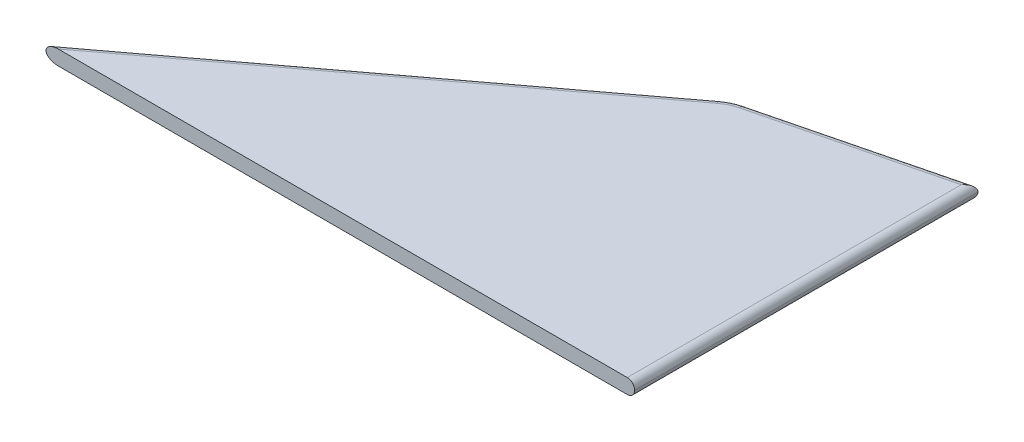
SolidWorks part; units mm, degrees
ref_plane "Front Plane" through (0, 0, 0) normal (0, 0, 1) x (1, 0, 0)
ref_plane "Top Plane" through (0, 0, 0) normal (0, 1, 0) x (1, 0, 0)
ref_plane "Right Plane" through (0, 0, 0) normal (1, 0, 0) x (0, 0, -1)
sketch "Sketch1" plane through (0, 0, 0) normal (0, 1, 0) x (1, 0, 0)
  line L0 (0, 0) -> (120, 0)
  line L1 (120, 0) -> (120, 70)
  line L2 (120, 70) -> (80, 60)
  line L3 (80, 60) -> (0, 0)
  dimension "D1" = 120
  dimension "D2" = 70
  dimension "D3" = 80
  dimension "D4" = 60
extrude "Boss-Extrude1" add sketch "Sketch1" along normal blind 3
fillet "Fillet2" radius 10 1 edges at (80, 1.5, -60)
fillet "Fillet1" radius 1.5 8 edges at (120, 3, -35) (120, 0, -35) (100.9796, 3, -65.2449) (100.9796, 0, -65.2449) (39.1922, 0, -29.3942) (39.1922, 3, -29.3942) (80.0868, 0, -59.8177) (80.0868, 3, -59.8177)
